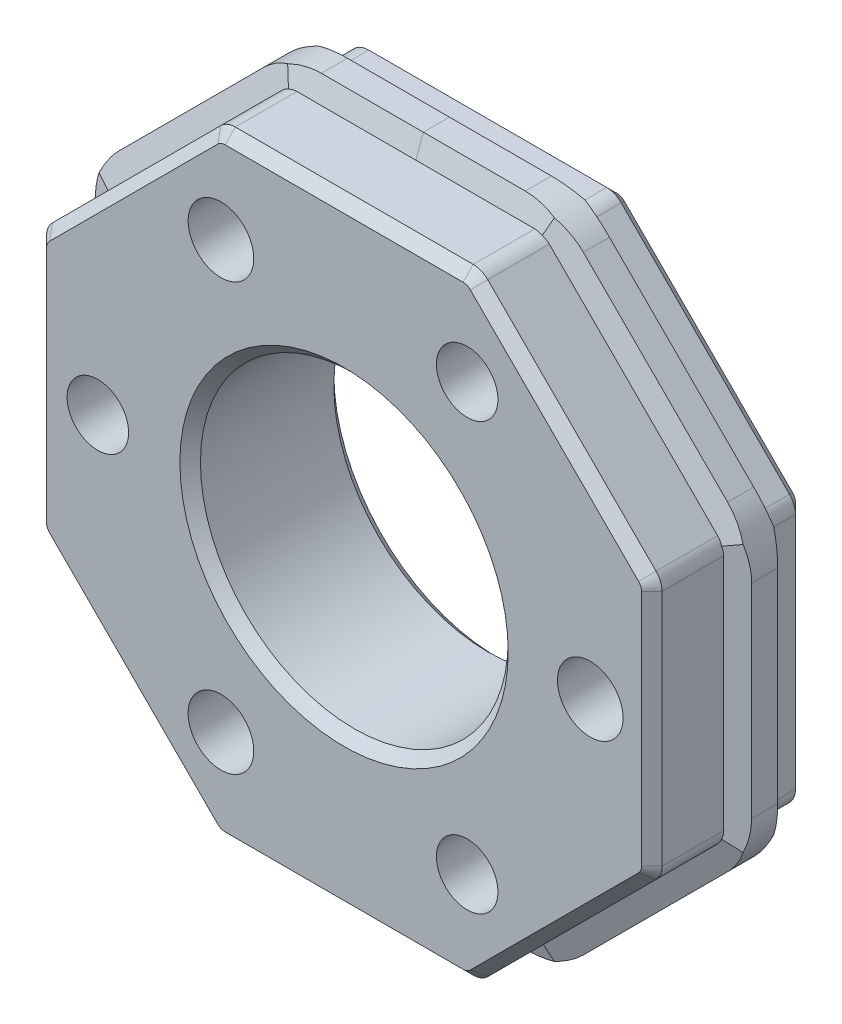
SolidWorks part; units mm, degrees
material "6061 合金"
ref_plane "前视基准面" through (0, 0, 0) normal (0, 0, 1) x (1, 0, 0)
ref_plane "上视基准面" through (0, 0, 0) normal (0, 1, 0) x (1, 0, 0)
ref_plane "右视基准面" through (0, 0, 0) normal (1, 0, 0) x (0, 0, -1)
other "Configuration Table"
sketch "草图1" plane through (0, 0, 0) normal (0, 0, 1) x (1, 0, 0)
  line L1 (-16, 16) -> (16, 16)
  line L2 (-16, 16) -> (-16, -16)
  line L3 (-16, -16) -> (16, -16)
  line L4 (16, 16) -> (16, -16)
  line L5 (0, -16) -> (0, 16) construction
  line L6 (-16, 0) -> (16, 0) construction
  circle A0 centre (0, 0) radius 7.5
  circle A1 centre (0, 0) radius 18 construction
  circle A2 centre (0, 0) radius 12 construction
  dimension "D1" = 36
  dimension "D2" = 15
  dimension "D3" = 24
  dimension "D6" = 32
  dimension "D7" = 32
extrude "凸台-拉伸1" add sketch "草图1" along normal mid plane 6
sketch "草图23" plane through (0, 0, 3) normal (0, 0, 1) x (1, 0, 0)
  line L0 (16, 16) -> (16, -16)
  line L8 (-16, -16) -> (16, -16)
  line L11 (16, -16) -> (16, 16)
  line L12 (16, -16) -> (16, 16)
  line L14 (16, 16) -> (-16, 16)
  line L15 (-16, 16) -> (-16, -16)
  line L16 (-16, -16) -> (16, -16)
  line L22 (16, 16) -> (-16, 16)
  line L23 (-16, 16) -> (-16, -16)
  line M23 (-16, -16) -> (16, -16)
  line M25 (16, -16) -> (16, 16)
  line M35 (16, 16) -> (-16, 16)
  line M37 (-16, 16) -> (-16, -16)
  circle M39 centre (0, 0) radius 7.5
  dimension "D1" = 0
extrude "凸台-拉伸4" add sketch "草图23" along normal blind 1.5 contours M23 M25 M35 M37 M39 region at (15.5475, 0, 3)
sketch "草图8" plane through (0, 0, -3) normal (0, 0, -1) x (-1, 0, 0)
  circle A0 centre (0, 0) radius 12 construction
  point P0 (-12, 0)
  point P1 (6, 10.3923)
  point P9 (6, -10.3923)
  dimension "D1" = 24
  dimension "D2" = 3
hole_wizard "M3 六角圆柱头螺钉的柱形沉头孔1" positions "草图8" profile "草图9" counterbore size "M3" standard "GB" end condition through all
sketch "草图9" plane through (12, 0, -3) normal (1, 0, 0) x (0, 1, 0)
  line L0 (0, 0) -> (0, 7.5)
  line L1 (0, 7.5) -> (1.6, 7.5)
  line L3 (1.6, 7.5) -> (1.6, 5)
  line L4 (1.6, 5) -> (2.85, 5)
  line L5 (2.85, 5) -> (2.85, 0)
  line L7 (2.85, 0) -> (0, 0)
  line L11 (0, -6.35) -> (0, 107.95) construction
  dimension "通孔孔直径" = 3.2
  dimension "通孔孔深度" = 7.5
  dimension "柱形沉头孔直径" = 5.7
  dimension "柱形沉头孔深度" = 5
sketch "草图24" plane through (0, 0, 4.5) normal (0, 0, 1) x (1, 0, 0)
  circle A0 centre (0, 0) radius 12 construction
  point P0 (-12, 0)
  point P13 (6, 10.3923)
  point P14 (6, -10.3923)
  dimension "D1" = 24
  dimension "D2" = 3
hole_wizard "Ø3.0mm 暗销孔1" positions "草图24" profile "草图25" hole size "Ø3.0" standard "BSI"
sketch "草图25" plane through (-12, 0, 4.5) normal (1, 0, 0) x (0, -1, 0)
  line L0 (0, 0) -> (0, 4.9013)
  line L1 (0, 4.9013) -> (1.5, 4)
  line L2 (1.5, 4) -> (1.5, 0)
  line L5 (1.5, 0) -> (0, 0)
  line L10 (0, 4.9013) -> (-1.5, 4) construction
  line L11 (0, -6.35) -> (0, 107.95) construction
  dimension "孔直径" = 3
  dimension "孔深度" = 4
  dimension "导头角度" = 118
ref_plane "基准面1" through (0, 0, 0) normal (0, 0, -1) x (-1, 0, 0)
sketch "草图26" plane through (0, 0, -3) normal (0, 0, -1) x (-1, 0, 0)
  circle A0 centre (0, 0) radius 15
  dimension "D1" = 30
extrude "切除-拉伸1" cut sketch "草图26" against normal through all flip side to cut
sketch "草图35" plane through (0, 0, 4.5) normal (0, 0, 1) x (1, 0, 0)
  line L0 (-18.5745, 0) -> (16.9837, 0) construction
ref_plane "基准面2" through (0, 0, 0) normal (0, -1, 0) x (1, 0, 0)
sketch "草图42" plane through (0, 0, -3) normal (0, 0, -1) x (-1, 0, 0)
  line L1 (-6.2132, 15) -> (-15, 6.2132)
  line L2 (-15, 6.2132) -> (-15, -6.2132)
  line L3 (-15, -6.2132) -> (-6.2132, -15)
  line L4 (-6.2132, -15) -> (6.2132, -15)
  line L5 (6.2132, -15) -> (15, -6.2132)
  line L6 (15, -6.2132) -> (15, 6.2132)
  line L7 (15, 6.2132) -> (6.2132, 15)
  line L8 (6.2132, 15) -> (-6.2132, 15)
  circle A0 centre (0, 0) radius 15 construction
  circle A1 centre (0, 0) radius 15 construction
  circle A2 centre (0, 0) radius 15
extrude "凸台-拉伸5" add sketch "草图42" against normal up to surface (7.5 mm away) contours A2 L8 L1 | A2 L7 L8 | A2 L6 L7 | A2 L5 L6 | A2 L4 L5 | A2 L3 L4 | A2 L2 L3 | A2 L1 L2 region at (5.8394, 14.0975, -3) region at (14.0975, 5.8394, -3) region at (-5.8394, 14.0975, -3) region at (14.0975, -5.8394, -3) region at (-14.0975, 5.8394, -3) region at (5.8394, -14.0975, -3) region at (-14.0975, -5.8394, -3) region at (-5.8394, -14.0975, -3) up to face at (7.5, 0, 4.5)
sketch "草图43" plane through (0, 0, 0) normal (1, 0, 0) x (0, 0, -1)
  line L1 (-1, 15) -> (1, 15)
  line L2 (-4.5, 15) -> (3, 15) construction
  line L3 (1, 15) -> (0.636, 16)
  line L4 (0.636, 16) -> (-0.636, 16)
  line L5 (-0.636, 16) -> (-1, 15)
  line L8 (3, 6.2132) -> (3, 15) construction
  line L9 (0, 22.7244) -> (0, -9.6288) construction
  dimension "D2" = 40
  dimension "D3" = 1
  dimension "D4" = 2
ref_plane "基准面3" through (0, 0, -1) normal (0, 0, -1) x (-1, 0, 0)
sketch "草图44" plane through (0, 0, -1) normal (0, 0, -1) x (-1, 0, 0)
  line L8 (-6.2132, 15) -> (-15, 6.2132)
  line L9 (-15, 6.2132) -> (-15, -6.2132)
  line L10 (-15, -6.2132) -> (-6.2132, -15)
  line L11 (-6.2132, -15) -> (6.2132, -15)
  line L12 (6.2132, -15) -> (15, -6.2132)
  line L13 (15, -6.2132) -> (15, 6.2132)
  line L14 (15, 6.2132) -> (6.2132, 15)
  line L15 (6.2132, 15) -> (-6.2132, 15)
  line L16 (-6.2132, 15) -> (-15, 6.2132)
  line L17 (-15, 6.2132) -> (-15, -6.2132)
  line L18 (-15, -6.2132) -> (-6.2132, -15)
  line L19 (-6.2132, -15) -> (6.2132, -15)
  line L20 (6.2132, -15) -> (15, -6.2132)
  line L21 (15, -6.2132) -> (15, 6.2132)
  line L22 (15, 6.2132) -> (6.2132, 15)
  line L23 (6.2132, 15) -> (-6.2132, 15)
  dimension "D1" = 0
sweep "扫描1" add profiles "草图43" path "草图44"
fillet "圆角1" radius 1 16 edges at (15, 6.2132, 2.75) (15, -6.2132, 2.75) (6.2132, -15, 2.75) (-6.2132, -15, 2.75) (-15, -6.2132, 2.75) (-15, 6.2132, 2.75) (6.2132, 15, 2.75) (-6.2132, 15, 2.75) (6.2132, 15, -2) (15, 6.2132, -2) (15, -6.2132, -2) (6.2132, -15, -2) (-6.2132, -15, -2) (-15, -6.2132, -2) (-15, 6.2132, -2) (-6.2132, 15, -2)
chamfer "倒角1" distance 0.5 angle 45 34 edges at (0, -15, -3) (-6.1817, -14.9239, -3) (6.1817, -14.9239, -3) (-10.6066, -10.6066, -3) (10.6066, -10.6066, -3) (-14.9239, -6.1817, -3) (14.9239, -6.1817, -3) (-15, 0, -3) (15, 0, -3) (-14.9239, 6.1817, -3) (14.9239, 6.1817, -3) (-10.6066, 10.6066, -3) (10.6066, 10.6066, -3) (-6.1817, 14.9239, -3) (6.1817, 14.9239, -3) (0, 15, -3) (0, -15, 4.5) (-6.1817, -14.9239, 4.5) (6.1817, -14.9239, 4.5) (-10.6066, -10.6066, 4.5) (10.6066, -10.6066, 4.5) (-14.9239, -6.1817, 4.5) (14.9239, -6.1817, 4.5) (-15, 0, 4.5) (15, 0, 4.5) (-14.9239, 6.1817, 4.5) (14.9239, 6.1817, 4.5) (-10.6066, 10.6066, 4.5) (10.6066, 10.6066, 4.5) (-6.1817, 14.9239, 4.5) (6.1817, 14.9239, 4.5) (0, 15, 4.5) (7.5, 0, 4.5) (7.5, 0, -3)
fillet "圆角2" radius 4 8 edges at (6.6274, 16, 0) (-6.6274, 16, 0) (-16, 6.6274, 0) (-16, -6.6274, 0) (-6.6274, -16, 0) (6.6274, -16, 0) (16, -6.6274, 0) (16, 6.6274, 0)
